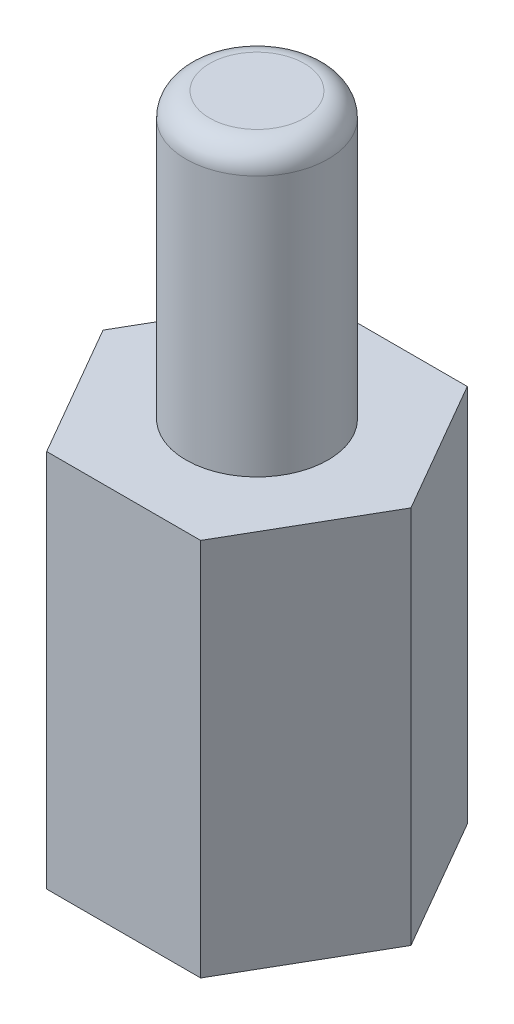
SolidWorks part; units mm, degrees
note: The reader was unsure of these and kept them because the rebuilt part matched: shared geometry of "草图1<2>".
ref_plane "前视基准面" through (0, 0, 0) normal (0, 0, 1) x (1, 0, 0)
ref_plane "上视基准面" through (0, 0, 0) normal (0, 1, 0) x (1, 0, 0)
ref_plane "右视基准面" through (0, 0, 0) normal (1, 0, 0) x (0, 0, -1)
sketch "草图1" plane through (0, 0, 0) normal (0, 1, 0) x (1, 0, 0)
  circle A0 centre (0, 0) radius 1.5
  dimension "D1" = 3
extrude "凸台-拉伸1" add sketch "草图1" along normal blind 14
fillet "圆角1" radius 0.5 1 edges at (0, 14, 1.5)
sketch "草图2" plane through (0, 0, 0) normal (0, 1, 0) x (1, 0, 0)
  line L1 (-1.625, 2.8146) -> (-3.25, 0)
  line L2 (-3.25, 0) -> (-1.625, -2.8146)
  line L3 (-1.625, -2.8146) -> (1.625, -2.8146)
  line L4 (1.625, -2.8146) -> (3.25, 0)
  line L5 (3.25, 0) -> (1.625, 2.8146)
  line L6 (1.625, 2.8146) -> (-1.625, 2.8146)
  circle A0 centre (0, 0) radius 3.25 construction
  circle A1 centre (0, 0) radius 1.5
  dimension "D1" = 3
  dimension "D2" = 6.5
extrude "凸台-拉伸2" add sketch "草图2" along normal blind 8
extrude "切除-拉伸1" cut sketch "草图1<2>" along normal blind 7
sketch "草图1<2>" plane through (0, 0, 0) normal (0, 1, 0) x (1, 0, 0) same geometry as "草图1"
